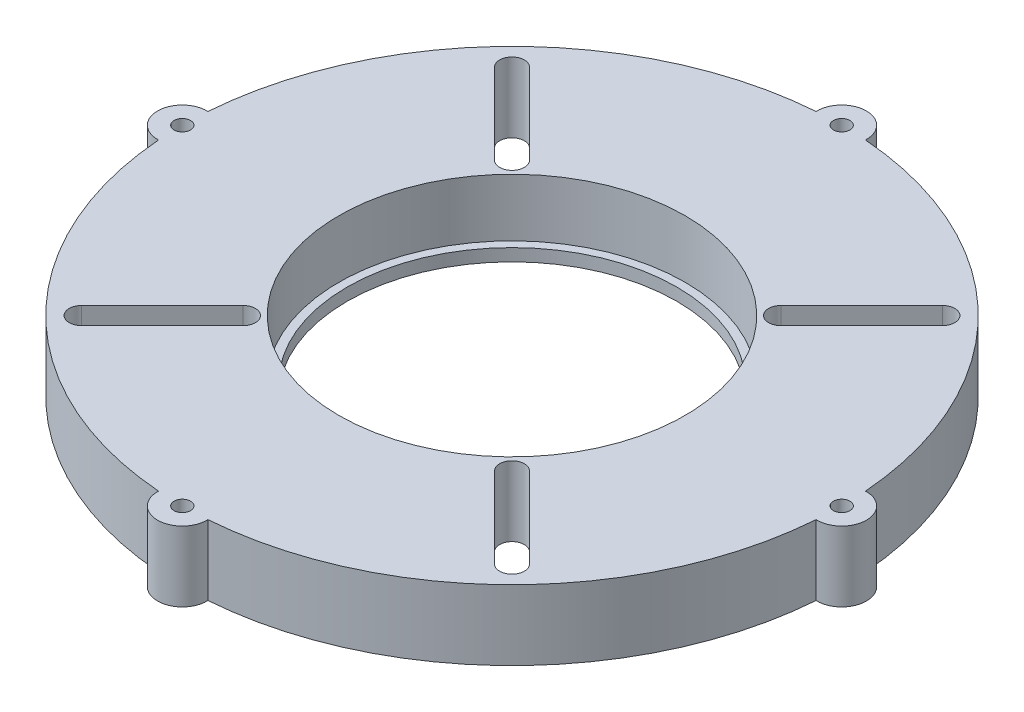
SolidWorks part; units mm, degrees
material "Aluminum 7075-T6 (2)"
ref_plane "Front Plane" through (0, 0, 0) normal (0, 0, 1) x (1, 0, 0)
ref_plane "Top Plane" through (0, 0, 0) normal (0, 1, 0) x (1, 0, 0)
ref_plane "Right Plane" through (0, 0, 0) normal (1, 0, 0) x (0, 0, -1)
sketch "Sketch1" plane through (0, 0, 0) normal (0, 1, 0) x (1, 0, 0)
  circle A0 centre (0, 0) radius 20
  circle A1 centre (0, 0) radius 40
extrude "Boss-Extrude1" add sketch "Sketch1" along normal blind 8.5 contours A1 | A0
sketch "Sketch2" plane through (0, 8.5, 0) normal (0, 1, 0) x (1, 0, 0)
  circle A0 centre (40, 0) radius 3
  circle A1 centre (40, 0) radius 1
extrude "Cut-Extrude2" cut sketch "Sketch2" against normal through all contours A1
extrude "Boss-Extrude3" add sketch "Sketch2<6>" against normal blind 8.5
sketch "Sketch2<6>" plane through (0, 8.5, 0) normal (0, 1, 0) x (1, 0, 0) same geometry as "Sketch2"
pattern_circular "CirPattern1" count 4 over 360 about axis through (0, 8.5, 0) along (0, 1, 0) of "Cut-Extrude2", "Boss-Extrude3"
sketch "Sketch4" plane through (0, 8.5, 0) normal (0, 1, 0) x (1, 0, 0)
  line L0 (-26.1099, -26.1099) -> (-16.3165, -16.3165) construction
  line L1 (-27.1706, -25.0493) -> (-17.3771, -15.2558)
  line L2 (-25.0493, -27.1706) -> (-15.2558, -17.3771)
  line L3 (-21.2132, -21.2132) -> (0, 0) construction
  arc A0 (-27.1706, -25.0493) -> (-25.0493, -27.1706) centre (-26.1099, -26.1099) ccw
  arc A1 (-15.2558, -17.3771) -> (-17.3771, -15.2558) centre (-16.3165, -16.3165) ccw
  circle A2 centre (0, 0) radius 20 construction
  point P2 (-21.2132, -21.2132)
  dimension "D1" = 13.85
  dimension "D2" = 1.5
  dimension "D3" = 23.075
extrude "Cut-Extrude4" cut sketch "Sketch4" against normal through all
pattern_circular "CirPattern3" count 4 over 360 about axis through (0, 8.5, 0) along (0, 1, 0) of "Cut-Extrude4"
sketch "Sketch7" plane through (0, 8.5, 0) normal (0, 1, 0) x (1, 0, 0)
  circle A0 centre (0, 0) radius 21
extrude "Cut-Extrude5" cut sketch "Sketch7" against normal blind 7
